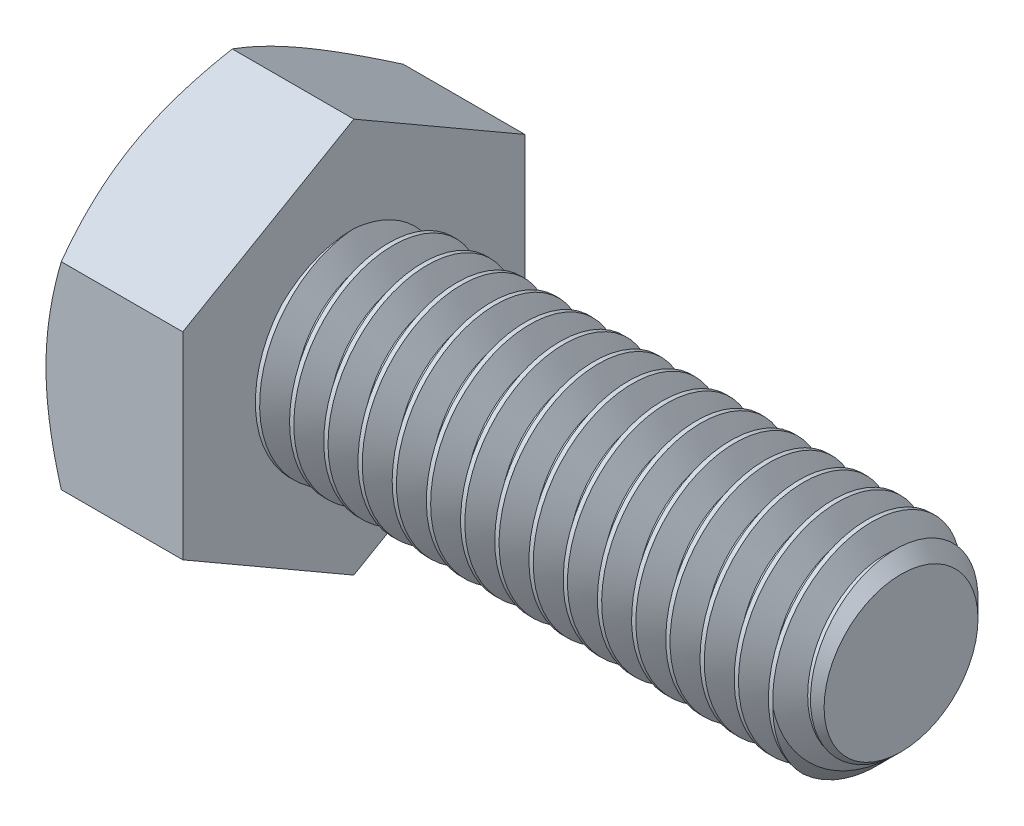
SolidWorks part; units mm, degrees
ref_plane "Front Plane" through (0, 0, 0) normal (0, 0, 1) x (1, 0, 0)
ref_plane "Top Plane" through (0, 0, 0) normal (0, 1, 0) x (1, 0, 0)
ref_plane "Right Plane" through (0, 0, 0) normal (1, 0, 0) x (0, 0, -1)
sketch "Sketch1" plane through (0, 0, 0) normal (0, 0, 1) x (1, 0, 0)
  line L0 (-10, 0) -> (10, 0) construction
  line L1 (-6, 5) -> (-6, -5) construction
  line L2 (-10, 5) -> (-10, -5) construction
  line L3 (10, 3) -> (10, -3) construction
  point P8 (6.5, -3)
  dimension "Thread Dia" = 6
  dimension "Hex" = 10
  dimension "Head Ht" = 4
  dimension "Length" = 16
  dimension "D1" = 3.5
ref_plane "Plane2" through (10, 0, 0) normal (1, 0, 0) x (0, 0, -1)
sketch "Sketch2" plane through (10, 0, 0) normal (1, 0, 0) x (0, 0, -1)
  circle A0 centre (0, 0) radius 3
extrude "Boss-Extrude1" add sketch "Sketch2" against normal up to vertex (16 mm away) up to point (-6, -5, 0)
sketch "Sketch4" plane through (10, 0, 0) normal (1, 0, 0) x (0, 0, -1)
  circle A1 centre (0, 0) radius 3
  circle A2 centre (0, 0) radius 3
  dimension "D1" = 0
curve "Helix/Spiral1" pitch 1 height 17 turns 17 parameters "Pitch"=1
chamfer "Chamfer1" distance 0.75 angle 45 1 edges at (10, 0, -3)
sketch "Sketch5" plane through (0, 0, 0) normal (0, 0, 1) x (1, 0, 0)
  line L0 (10, 3) -> (10.375, 2.3505)
  line L1 (10.375, 2.3505) -> (10.5, 2.3505)
  line L2 (10.5, 2.3505) -> (10.875, 3)
  line L3 (10, 3) -> (10.875, 3)
  line L4 (10.4375, 2.3505) -> (10.4375, 3) construction
  line L5 (10.1875, 2.6752) -> (10.6875, 2.6752) construction
  line L6 (10, -3) -> (10, 3) construction
  dimension "D1" = 60
  dimension "D2" = 0.125
  dimension "D3" = 0.5
sweep "Cut-Sweep1" cut profiles "Sketch5" path "Helix/Spiral1" align with end faces yes
sketch "Sketch3" plane through (-6, 0, 0) normal (-1, 0, 0) x (0, 0, 1)
  line L0 (0, 5) -> (0, -5) construction
  line L1 (-5, -2.8868) -> (0, -5.7735)
  line L2 (0, -5.7735) -> (5, -2.8868)
  line L3 (5, -2.8868) -> (5, 2.8868)
  line L4 (5, 2.8868) -> (0, 5.7735)
  line L5 (0, 5.7735) -> (-5, 2.8868)
  line L6 (-5, 2.8868) -> (-5, -2.8868)
  circle A0 centre (0, 0) radius 5 construction
extrude "Boss-Extrude2" add sketch "Sketch3" along normal up to vertex (4 mm away) up to point (-10, -5, 0)
sketch "Sketch6" plane through (-10, 0, 0) normal (-1, 0, 0) x (0, 0, 1)
  circle A0 centre (0, 0) radius 5 construction
  circle A1 centre (0, 0) radius 5
extrude "Cut-Extrude1" cut sketch "Sketch6" against normal through all draft 60 flip side to cut
sketch "Sketch7" plane through (-10, 0, 0) normal (-1, 0, 0) x (0, 0, 1)
  line L0 (0, 0) -> (0, 5) construction
  line L2 (0, 5) -> (0, -5) construction
  line L3 (-4.3301, 2.5) -> (4.3301, 2.5) construction
  circle A1 centre (0, 0) radius 5 construction
  text T0 "10.9" font "Arial" height in points 6
  point P8 (0, 2.5)
extrude "Cut-Extrude2" cut sketch "Sketch7" against normal blind 0.25
sketch "Sketch9" plane through (0, 0, 0) normal (0, 0, 1) x (1, 0, 0)
  line L0 (-6, 3) -> (-6, 0)
  line L1 (-6, 0) -> (-41, 0)
  line L2 (-41, 0) -> (-44, 3)
  line L3 (-44, 3) -> (-6, 3)
  line L4 (-10, 0) -> (10, 0) construction
  line L5 (-6, 5) -> (-6, -5) construction
  line L6 (10, 3) -> (10, -3) construction
  dimension "D1" = 45
  dimension "MinThreadLg" = 54
revolve "Revolve1" [suppressed] add sketch "Sketch9" angle 360 about L1
equation "\"D2@Sketch5\" = \"Pitch@Helix/Spiral1\"*.125"
equation "\"D3@Sketch5\" = \"Pitch@Helix/Spiral1\"*.50"
equation "\"D3@Helix/Spiral1\" = \"Length@Sketch1\"+\"Pitch@Helix/Spiral1\""
equation "\"D1@Chamfer1\" = \"Pitch@Helix/Spiral1\"*.750"
equation "\"D1@Sketch1\" = \"Pitch@Helix/Spiral1\"*3.50"
